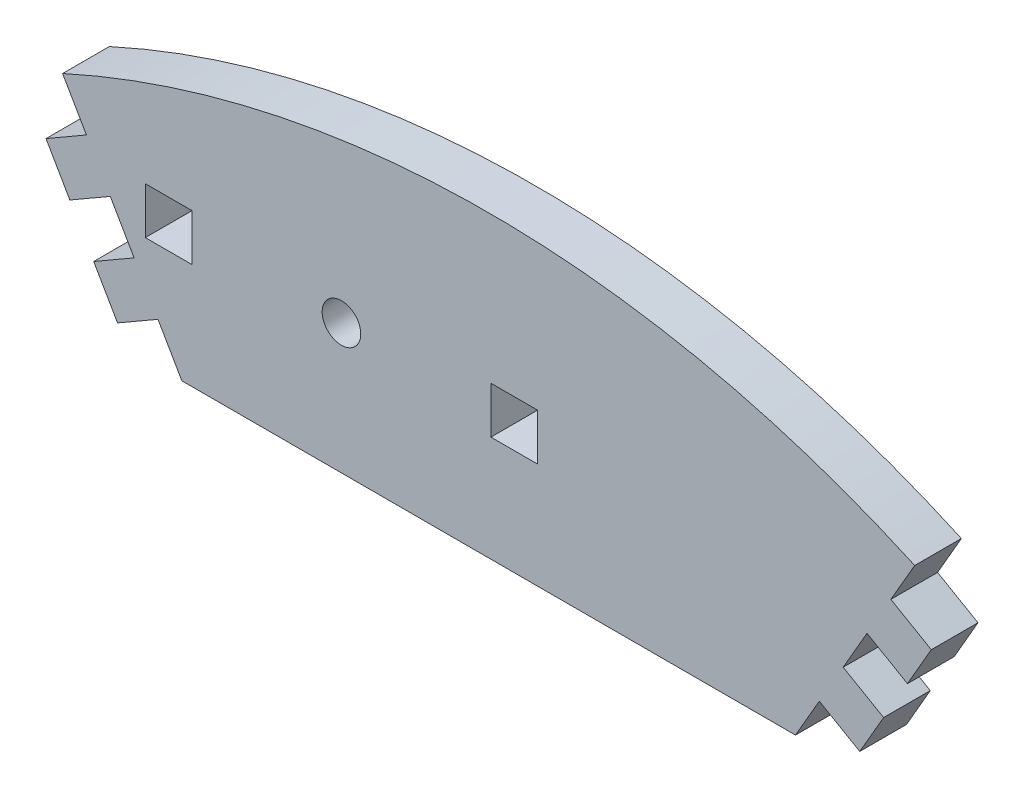
SolidWorks part; units mm, degrees
ref_plane "Front Plane" through (0, 0, 0) normal (0, 0, 1) x (1, 0, 0)
ref_plane "Top Plane" through (0, 0, 0) normal (0, 1, 0) x (1, 0, 0)
ref_plane "Right Plane" through (0, 0, 0) normal (1, 0, 0) x (0, 0, -1)
sketch "Sketch1" plane through (0, 0, 0) normal (0, 0, 1) x (1, 0, 0)
  line L0 (-32.85, 77.9867) -> (32.85, 77.9867)
  line L4 (-32.85, 77.9867) -> (-35.403, 82.4086)
  line L5 (0, 0) -> (0, 126.1957) construction
  line L7 (32.85, 77.9867) -> (35.403, 82.4086)
  line L8 (35.403, 82.4086) -> (39.7331, 79.9086)
  line L9 (39.7331, 79.9086) -> (42.2861, 84.3305)
  line L10 (42.2861, 84.3305) -> (37.956, 86.8305)
  line L11 (37.956, 86.8305) -> (40.509, 91.2525)
  line L12 (40.509, 91.2525) -> (44.8391, 88.7525)
  line L13 (44.8391, 88.7525) -> (47.3921, 93.1744)
  line L14 (47.3921, 93.1744) -> (43.062, 95.6744)
  line L15 (43.062, 95.6744) -> (45.615, 100.0963)
  line L16 (-43.062, 95.6744) -> (-45.615, 100.0963)
  line L17 (-47.3921, 93.1744) -> (-43.062, 95.6744)
  line L18 (-44.8391, 88.7525) -> (-47.3921, 93.1744)
  line L19 (-40.509, 91.2525) -> (-44.8391, 88.7525)
  line L20 (-37.956, 86.8305) -> (-40.509, 91.2525)
  line L21 (-42.2861, 84.3305) -> (-37.956, 86.8305)
  line L22 (-39.7331, 79.9086) -> (-42.2861, 84.3305)
  line L23 (-35.403, 82.4086) -> (-39.7331, 79.9086)
  arc A0 (-45.615, 100.0963) -> (45.615, 100.0963) centre (0, 0) cw
  dimension "D1" = 120
  dimension "D2" = 110
  dimension "D3" = 25.53
  dimension "D4" = 5
  dimension "D5" = 65.7
extrude "Boss-Extrude1" add sketch "Sketch1" along normal blind 5
sketch "Sketch2" plane through (0, 0, 5) normal (0, 0, 1) x (1, 0, 0)
  line L0 (0, 111.5372) -> (0, 71.5875) construction
  line L1 (0, -2.75) -> (0, 2.75) construction
  line L3 (0.24, 94.3078) -> (5.24, 94.3078)
  line L4 (0.24, 94.3078) -> (0.24, 89.3078)
  line L5 (0.24, 89.3078) -> (5.24, 89.3078)
  line L6 (5.24, 94.3078) -> (5.24, 89.3078)
  line L11 (-32.85, 77.9867) -> (-17.0875, 77.9867) construction
  line L12 (-32.85, 77.9867) -> (32.85, 77.9867) construction
  line L14 (-31.76, 89.3078) -> (-36.76, 89.3078)
  line L15 (-31.76, 89.3078) -> (-31.76, 94.3078)
  line L16 (-31.76, 94.3078) -> (-36.76, 94.3078)
  line L17 (-36.76, 89.3078) -> (-36.76, 94.3078)
  circle A0 centre (-15.76, 91.8974) radius 2.0675
  dimension "D4" = 4.135
  dimension "D1" = 32
  dimension "D2" = 5
  dimension "D3" = 5
  dimension "D5" = 15.7625
  dimension "D7" = 5
extrude "Cut-Extrude1" cut sketch "Sketch2" against normal through all
